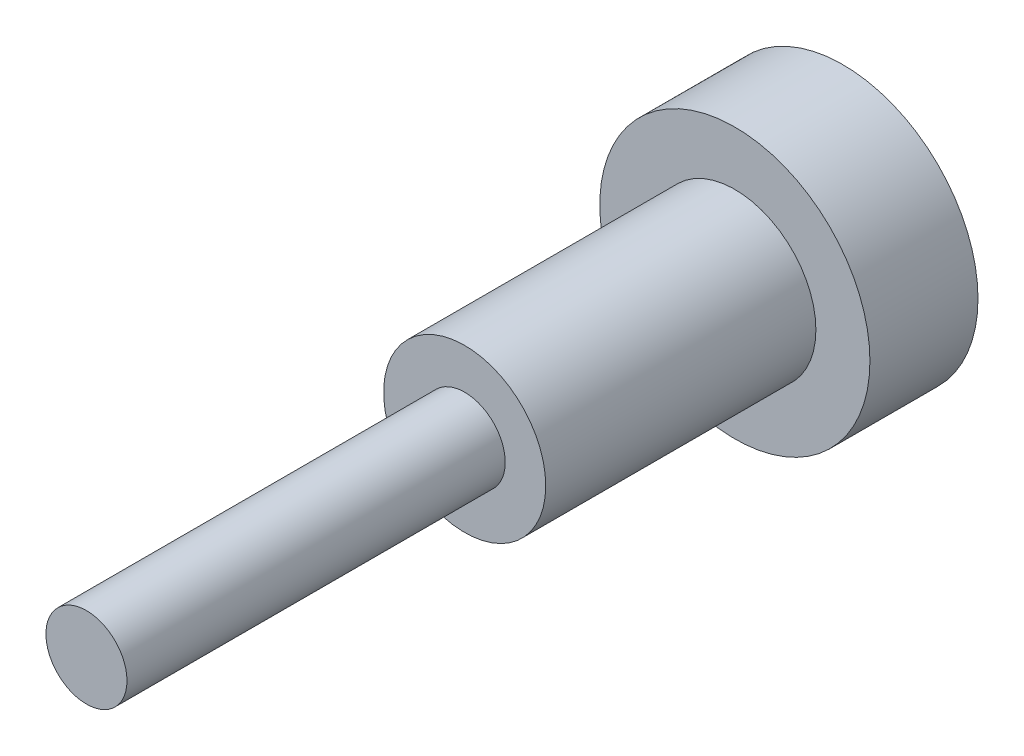
SolidWorks part; units mm, degrees
ref_plane "Ebene vorne" through (0, 0, 0) normal (0, 0, 1) x (1, 0, 0)
ref_plane "Ebene oben" through (0, 0, 0) normal (0, 1, 0) x (1, 0, 0)
ref_plane "Ebene rechts" through (0, 0, 0) normal (1, 0, 0) x (0, 0, -1)
sketch "Sketch1" plane through (0, 0, 0) normal (0, 0, 1) x (1, 0, 0)
  circle A0 centre (0, 0) radius 0.75
  circle A1 centre (0, 0) radius 1.5
  circle A2 centre (0, 0) radius 2.5
  dimension "D1" = 1.5
  dimension "D2" = 3
  dimension "D3" = 5
extrude "Boss-Extrude1" add sketch "Sketch1" along normal blind 12 contours A0 region at (0, 0, 0)
extrude "Boss-Extrude2" add sketch "Sketch1<3>" along normal blind 5 contours A1 A0 region at (-1.4576, 0, 0)
sketch "Sketch1<3>" plane through (0, 0, 0) normal (0, 0, 1) x (1, 0, 0) same geometry as "Sketch1"
extrude "Boss-Extrude3" add sketch "Sketch1<4>" against normal blind 2 contours A2 A1 | A1 A0 | A0 region at (0, 0, 0) region at (-1.4576, 0, 0) region at (-2.4293, 0, 0)
sketch "Sketch1<4>" plane through (0, 0, 0) normal (0, 0, 1) x (1, 0, 0) same geometry as "Sketch1"
